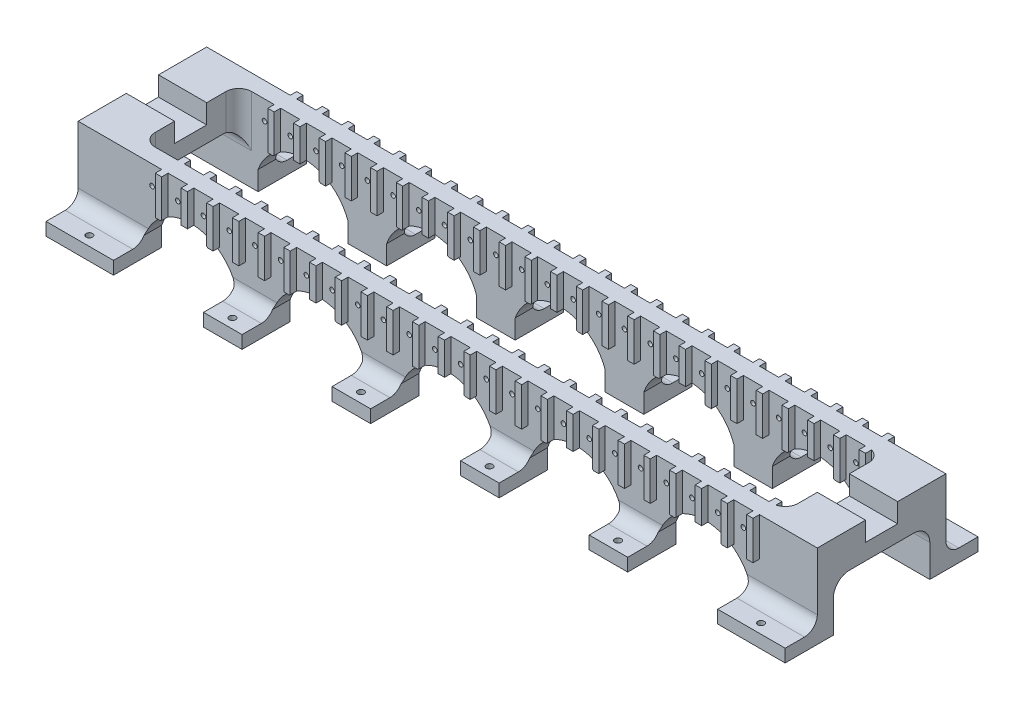
SolidWorks part; units mm, degrees
ref_plane "Front Plane" through (0, 0, 0) normal (0, 0, 1) x (1, 0, 0)
ref_plane "Top Plane" through (0, 0, 0) normal (0, 1, 0) x (1, 0, 0)
ref_plane "Right Plane" through (0, 0, 0) normal (1, 0, 0) x (0, 0, -1)
sketch "Sketch1" plane through (0, 0, 0) normal (0, 1, 0) x (1, 0, 0)
  line L1 (-50, -7.5) -> (50, -7.5)
  line L2 (-50, -7.5) -> (-50, 7.5)
  line L3 (-50, 7.5) -> (50, 7.5)
  line L4 (50, -7.5) -> (50, 7.5)
  line L5 (-50, -7.5) -> (50, 7.5) construction
  line L6 (-50, 7.5) -> (50, -7.5) construction
  line L7 (-57.5, -10) -> (57.5, -10)
  line L8 (-57.5, -10) -> (-57.5, 10)
  line L9 (-57.5, 10) -> (57.5, 10)
  line L10 (57.5, -10) -> (57.5, 10)
  line L11 (-57.5, -10) -> (57.5, 10) construction
  line L12 (-57.5, 10) -> (57.5, -10) construction
  point P0 (0, 0)
  point P6 (0, 0)
  dimension "D1" = 15
  dimension "D2" = 20
  dimension "D3" = 100
  dimension "D4" = 115
extrude "Boss-Extrude1" add sketch "Sketch1" along normal blind 13
ref_plane "Elec_Plane" through (0, 10, 0) normal (0, 1, 0) x (1, 0, 0)
sketch "Sketch2" plane through (57.5, 0, 0) normal (1, 0, 0) x (0, 0, -1)
  line L0 (0, 0) -> (0, 13) construction
  line L1 (-10, 0) -> (10, 0) construction
  line L2 (4.675, 10) -> (-4.675, 10) construction
  line L3 (0, 0) -> (0, 13) construction
  line L4 (-10, 13) -> (10, 13) construction
  line L5 (-2.5, 13) -> (2.5, 13)
  line L6 (-7.5, 0) -> (7.5, 0)
  line L7 (-7.5, 0) -> (-7.5, 7.5)
  line L8 (-7.5, 7.5) -> (7.5, 7.5)
  line L9 (7.5, 0) -> (7.5, 7.5)
  line L10 (-2.5, 13) -> (-2.5, 10)
  line L11 (-2.5, 10) -> (2.5, 10)
  line L12 (2.5, 13) -> (2.5, 10)
  dimension "D1" = 15
  dimension "D2" = 7.5
  dimension "D4" = 5
extrude "Cut-Extrude1" cut sketch "Sketch2" against normal through all
fillet "Fillet1" radius 2.5 4 edges at (53.75, 7.5, 7.5) (53.75, 7.5, -7.5) (-53.75, 7.5, -7.5) (-53.75, 7.5, 7.5) tangent propagation no
sketch "Sketch3" plane through (0, 0, 10) normal (0, 0, 1) x (1, 0, 0)
  line L0 (-57.5, 10) -> (57.5, 10) construction
  line L1 (-57.5, 13) -> (-57.5, 0) construction
  line L2 (57.5, 13) -> (57.5, 0) construction
  line L3 (-57.5, 13) -> (57.5, 13) construction
  line L4 (-50, 10) -> (-50, 13) construction
  line L5 (4.675, 10) -> (-4.675, 10) construction
  circle A0 centre (-46, 10) radius 0.36
  dimension "D2" = 0.72
  dimension "D3" = 4
extrude "Cut-Extrude2" cut sketch "Sketch3" against normal through all
sketch "Sketch12" plane through (0, 0, 10) normal (0, 0, 1) x (1, 0, 0)
  line L0 (4.675, 10) -> (-4.675, 10) construction
  line L1 (-44.5, 7) -> (-43.5, 7)
  line L2 (-44.5, 7) -> (-44.5, 13)
  line L3 (-44.5, 13) -> (-43.5, 13)
  line L4 (-43.5, 7) -> (-43.5, 13)
  line L5 (-44.5, 7) -> (-43.5, 13) construction
  line L6 (-44.5, 13) -> (-43.5, 7) construction
  line L7 (-57.5, 13) -> (57.5, 13) construction
  point P0 (-44, 10)
  dimension "D1" = 1
  dimension "D3" = 2
extrude "Boss-Extrude4" add sketch "Sketch12" along normal blind 1 and the other way blind 3.5
mirror "Mirror1" about plane through (0, 0, 0) normal (0, 0, 1) of "Boss-Extrude4"
pattern_linear "LPattern1" count 24 spacing 4 along (1, 0, 0) of "Cut-Extrude2", "Boss-Extrude4", "Mirror1"
sketch "Sketch6" plane through (0, 0, 0) normal (0, -1, 0) x (1, 0, 0)
  line L0 (-57.5, -10) -> (-57.5, -7.5) construction
  line L1 (57.5, -10) -> (-57.5, -10)
  line L2 (57.5, -10) -> (57.5, -15)
  line L3 (57.5, -15) -> (-57.5, -15)
  line L4 (-57.5, -10) -> (-57.5, -15)
  line L5 (57.5, 10) -> (57.5, 7.5) construction
  line L6 (57.5, 10) -> (-57.5, 10)
  line L7 (57.5, 10) -> (57.5, 15)
  line L8 (57.5, 15) -> (-57.5, 15)
  line L9 (-57.5, 10) -> (-57.5, 15)
  line L10 (-57.5, 7.5) -> (-57.5, 10) construction
  line L11 (-57.5, 10) -> (57.5, 10) construction
  dimension "D1" = 5
  dimension "D2" = 5
extrude "Boss-Extrude2" add sketch "Sketch6" against normal blind 2
ref_plane "Plane4" through (0, 2, 0) normal (0, 1, 0) x (1, 0, 0)
fillet "Fillet2" radius 2 2 edges at (0, 2, -10) (0, 2, 10)
sketch "Sketch5" plane through (0, 0, 10) normal (0, 0, 1) x (1, 0, 0)
  line L0 (-57.5, 0) -> (57.5, 0) construction
  line L1 (-50, 0) -> (-50, 13) construction
  line L2 (-57.5, 13) -> (-44.5, 13) construction
  line L3 (-47, 3) -> (-33, 3) construction
  line L4 (-47, 3) -> (-47, 0)
  line L5 (-47, 0) -> (-33, 0)
  line L6 (-33, 0) -> (-33, 3)
  line L7 (-40, 3) -> (-40, 0) construction
  line L8 (-40, 8) -> (-58.1515, 8) construction
  arc A0 (-47, 3) -> (-33, 3) centre (-40, 0.6) cw
  dimension "D1" = 10
  dimension "D2" = 5
  dimension "D3" = 3
  dimension "D4" = 14
extrude "Cut-Extrude4" cut sketch "Sketch5" against normal through all both and the other way through all
pattern_linear "LPattern2" count 5 spacing 20 along (1, 0, 0) of "Cut-Extrude4"
sketch "Sketch7" plane through (0, 2, 0) normal (0, 1, 0) x (1, 0, 0)
  line L0 (52.25, 15) -> (52.25, 13.5) construction
  line L1 (47, 15) -> (57.5, 15) construction
  line L2 (52.25, 13.5) -> (57.5, 13.5) construction
  line L3 (-57.5, 13.5) -> (-52.25, 13.5) construction
  line L4 (52.25, -15) -> (52.25, -13.5) construction
  line L5 (57.5, -15) -> (47, -15) construction
  line L6 (57.5, -13.5) -> (52.25, -13.5) construction
  line L7 (-57.5, 12) -> (-57.5, 15) construction
  line L8 (57.5, -12) -> (57.5, -15) construction
  line L9 (57.5, 15) -> (57.5, 12) construction
  line L10 (-52.25, 13.5) -> (-52.25, 15) construction
  line L11 (-57.5, 15) -> (-47, 15) construction
  line L12 (-52.25, -15) -> (-52.25, -13.5) construction
  line L13 (-47, -15) -> (-57.5, -15) construction
  line L14 (-52.25, -13.5) -> (-47, -13.5) construction
  line L15 (-47, -15) -> (-47, -12) construction
  circle A0 centre (52.25, 13.5) radius 0.5
  circle A1 centre (52.25, -13.5) radius 0.5
  circle A2 centre (-52.25, -13.5) radius 0.5
  circle A3 centre (-52.25, 13.5) radius 0.5
  dimension "D1" = 1
extrude "Cut-Extrude5" cut sketch "Sketch7" against normal blind 2
ref_plane "Plane3" through (-30, 0, 0) normal (-1, 0, 0) x (0, 0, 1)
sketch "Sketch10" plane through (0, 2, 0) normal (0, 1, 0) x (1, 0, 0)
  line L0 (-30, 7.0504) -> (-30, -7.0504) construction
  line L1 (-52.25, -13.5) -> (-30, -13.5) construction
  line L2 (-30, -13.5) -> (-30, 13.5) construction
  line L3 (-52.25, 13.5) -> (-30, 13.5) construction
  circle A0 centre (-30, -13.5) radius 0.5
  circle A1 centre (-30, 13.5) radius 0.5
  circle A2 centre (-52.25, 13.5) radius 0.5 construction
extrude "Cut-Extrude6" cut sketch "Sketch10" against normal blind 10
sketch "Sketch11" plane through (0, 10, 0) normal (0, 1, 0) x (1, 0, 0)
  line L0 (50, 7.5) -> (48.5, 7.5) construction
  line L1 (-31.5, 7.5) -> (-28.5, 7.5)
  line L2 (-31.5, 7.5) -> (-31.5, -7.5)
  line L3 (-31.5, -7.5) -> (-28.5, -7.5)
  line L4 (-28.5, 7.5) -> (-28.5, -7.5)
  line L5 (-50, -7.5) -> (-44.5, -7.5) construction
  line L7 (-30, 7.5) -> (-30, -7.5) construction
  line L8 (-30, 7.0504) -> (-30, -7.0504) construction
  dimension "D1" = 3
extrude "Boss-Extrude3" [suppressed] add sketch "Sketch11" against normal blind 2 from offset 2 offset against normal yes
fillet "Fillet4" [suppressed] radius 3
pattern_linear "LPattern3" count 4 spacing 20 along (1, 0, 0) of "Fillet4", "Boss-Extrude3", "Cut-Extrude6"
fillet "Fillet5" radius 2 4 edges at (50, 9, -7.5) (50, 9, 7.5) (-50, 9, -7.5) (-50, 9, 7.5)
